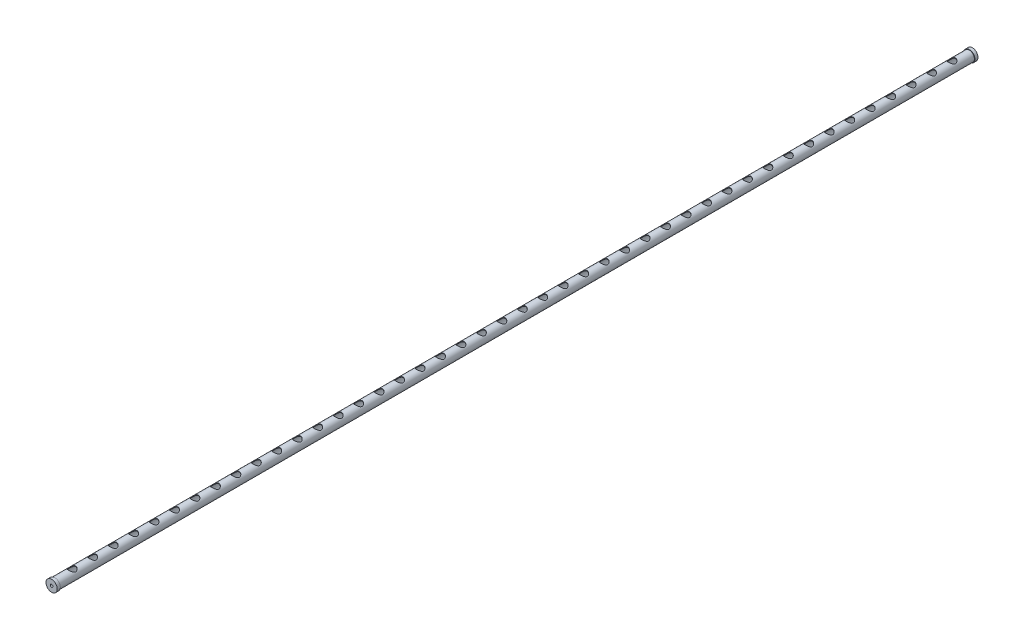
SolidWorks part; units mm, degrees
ref_plane "Alzado" through (0, 0, 0) normal (0, 0, 1) x (1, 0, 0)
ref_plane "Planta" through (0, 0, 0) normal (0, 1, 0) x (1, 0, 0)
ref_plane "Vista lateral" through (0, 0, 0) normal (1, 0, 0) x (0, 0, -1)
sketch "Croquis1" plane through (0, 0, 0) normal (0, 0, 1) x (1, 0, 0)
  circle A0 centre (0, 0) radius 50
  circle A1 centre (0, 0) radius 45
extrude "Saliente-Extruir1" add sketch "Croquis1" along normal blind 9000
ref_plane "Plano1" through (0, 50, 0) normal (0, 1, 0) x (1, 0, 0)
sketch "Croquis2" plane through (0, 50, 0) normal (0, 1, 0) x (1, 0, 0)
  line L13 (0, -7000) -> (0, -6980) construction
  circle A0 centre (0, -8800) radius 35
  circle A1 centre (0, -8600) radius 35
  circle A2 centre (0, -8400) radius 35
  circle A3 centre (0, -8200) radius 35
  circle A4 centre (0, -8000) radius 35
  circle A5 centre (0, -7800) radius 35
  circle A6 centre (0, -7600) radius 35
  circle A7 centre (0, -7400) radius 35
  circle A8 centre (0, -7200) radius 35
  circle A9 centre (0, -7000) radius 35
  circle A10 centre (0, -6800) radius 35
  circle A11 centre (0, -6600) radius 35
  circle A12 centre (0, -6400) radius 35
  circle A13 centre (0, -6200) radius 35
  circle A14 centre (0, -6000) radius 35
  circle A15 centre (0, -5800) radius 35
  circle A16 centre (0, -5600) radius 35
  circle A17 centre (0, -5400) radius 35
  circle A18 centre (0, -5200) radius 35
  circle A19 centre (0, -5000) radius 35
  circle A20 centre (0, -4800) radius 35
  circle A21 centre (0, -4600) radius 35
  circle A22 centre (0, -4400) radius 35
  circle A23 centre (0, -4200) radius 35
  circle A24 centre (0, -4000) radius 35
  circle A25 centre (0, -3800) radius 35
  circle A26 centre (0, -3600) radius 35
  circle A27 centre (0, -3400) radius 35
  circle A28 centre (0, -3200) radius 35
  circle A29 centre (0, -3000) radius 35
  circle A30 centre (0, -2800) radius 35
  circle A31 centre (0, -2600) radius 35
  circle A32 centre (0, -2400) radius 35
  circle A33 centre (0, -2200) radius 35
  circle A34 centre (0, -2000) radius 35
  circle A35 centre (0, -1800) radius 35
  circle A36 centre (0, -1600) radius 35
  circle A37 centre (0, -1400) radius 35
  circle A38 centre (0, -1200) radius 35
  circle A39 centre (0, -1000) radius 35
  circle A40 centre (0, -800) radius 35
  circle A41 centre (0, -600) radius 35
  circle A42 centre (0, -400) radius 35
  circle A43 centre (0, -200) radius 35
extrude "Cortar-Extruir1" cut sketch "Croquis2" against normal blind 30
sketch "Croquis3" plane through (0, 0, 0) normal (0, 0, 1) x (1, 0, 0)
  circle A0 centre (0, 0) radius 55
  circle A1 centre (0, 0) radius 12.7
extrude "Saliente-Extruir2" add sketch "Croquis3" along normal blind 30
ref_plane "Plano2" through (0, 0, 9000) normal (0, 0, 1) x (1, 0, 0)
sketch "Croquis4" plane through (0, 0, 9000) normal (0, 0, 1) x (1, 0, 0)
  circle A0 centre (0, 0) radius 12.7
  circle A1 centre (0, 0) radius 55
extrude "Saliente-Extruir3" add sketch "Croquis4" against normal blind 30
